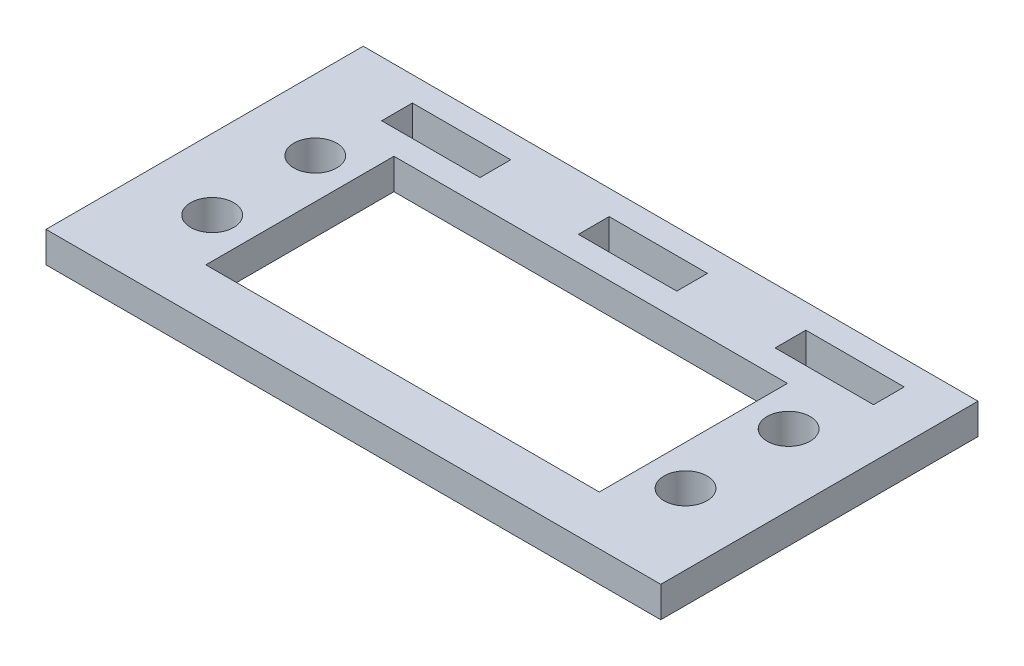
SolidWorks part; units mm, degrees
ref_plane "Front Plane" through (0, 0, 0) normal (0, 0, 1) x (1, 0, 0)
ref_plane "Top Plane" through (0, 0, 0) normal (0, 1, 0) x (1, 0, 0)
ref_plane "Right Plane" through (0, 0, 0) normal (1, 0, 0) x (0, 0, -1)
sketch "Sketch1" plane through (0, 0, 0) normal (0, 1, 0) x (1, 0, 0)
  line L0 (26.67, -9.7155) -> (31.75, -9.7155) construction
  line L1 (31.75, 17.9705) -> (-31.75, 17.9705)
  line L2 (31.75, 17.9705) -> (31.75, -14.7955)
  line L3 (31.75, -14.7955) -> (-31.75, -14.7955)
  line L4 (-31.75, 17.9705) -> (-31.75, -14.7955)
  line L5 (26.67, -9.7155) -> (26.67, -14.7955) construction
  line L6 (-26.67, -9.7155) -> (-31.75, -9.7155) construction
  line L7 (-26.67, 9.7155) -> (26.67, 9.7155) construction
  line L8 (-26.67, 9.7155) -> (-26.67, -9.7155) construction
  line L9 (-26.67, -9.7155) -> (26.67, -9.7155) construction
  line L10 (26.67, 9.7155) -> (26.67, -9.7155) construction
  line L11 (-26.67, 9.7155) -> (26.67, -9.7155) construction
  line L12 (-26.67, -9.7155) -> (26.67, 9.7155) construction
  line L13 (26.67, 15.4305) -> (26.67, 17.9705) construction
  line L14 (26.67, 15.4305) -> (16.51, 15.4305)
  line L15 (26.67, 15.4305) -> (26.67, 12.2555)
  line L16 (26.67, 12.2555) -> (16.51, 12.2555)
  line L17 (16.51, 15.4305) -> (16.51, 12.2555)
  line L18 (26.67, 15.4305) -> (16.51, 12.2555) construction
  line L19 (26.67, 12.2555) -> (16.51, 15.4305) construction
  line L20 (26.67, 12.2555) -> (26.67, 9.7155) construction
  line L21 (6.35, 15.4305) -> (6.35, 12.2555)
  line L22 (6.35, 15.4305) -> (-3.81, 15.4305)
  line L23 (6.35, 12.2555) -> (-3.81, 12.2555)
  line L24 (-3.81, 15.4305) -> (-3.81, 12.2555)
  line L25 (-13.97, 15.4305) -> (-13.97, 12.2555)
  line L26 (-13.97, 15.4305) -> (-24.13, 15.4305)
  line L27 (-13.97, 12.2555) -> (-24.13, 12.2555)
  line L28 (-24.13, 15.4305) -> (-24.13, 12.2555)
  line L30 (-20.32, -9.7155) -> (20.32, -9.7155)
  line L31 (-20.32, -9.7155) -> (-20.32, 9.7155)
  line L32 (-20.32, 9.7155) -> (20.32, 9.7155)
  line L33 (20.32, -9.7155) -> (20.32, 9.7155)
  line L34 (-20.32, -9.7155) -> (20.32, 9.7155) construction
  line L35 (-20.32, 9.7155) -> (20.32, -9.7155) construction
  circle A0 centre (-24.4475, 5.7119) radius 2.2225
  circle A1 centre (-24.4475, -4.935) radius 2.2225
  circle A2 centre (24.4475, 5.7119) radius 2.2225
  circle A3 centre (24.4475, -4.935) radius 2.2225
  point P0 (0, 0)
  point P4 (21.59, 13.843)
  point P6 (0, 0)
  point P20 (0, 0)
  dimension "D9" = 4.445
  dimension "D1" = 19.431
  dimension "D2" = 53.34
  dimension "D3" = 5.08
  dimension "D4" = 3.175
  dimension "D5" = 10.16
  dimension "D6" = 2.54
  dimension "D7" = 3
  dimension "D8" = 6.35
extrude "Boss-Extrude2" add sketch "Sketch1" along normal blind 3.175
